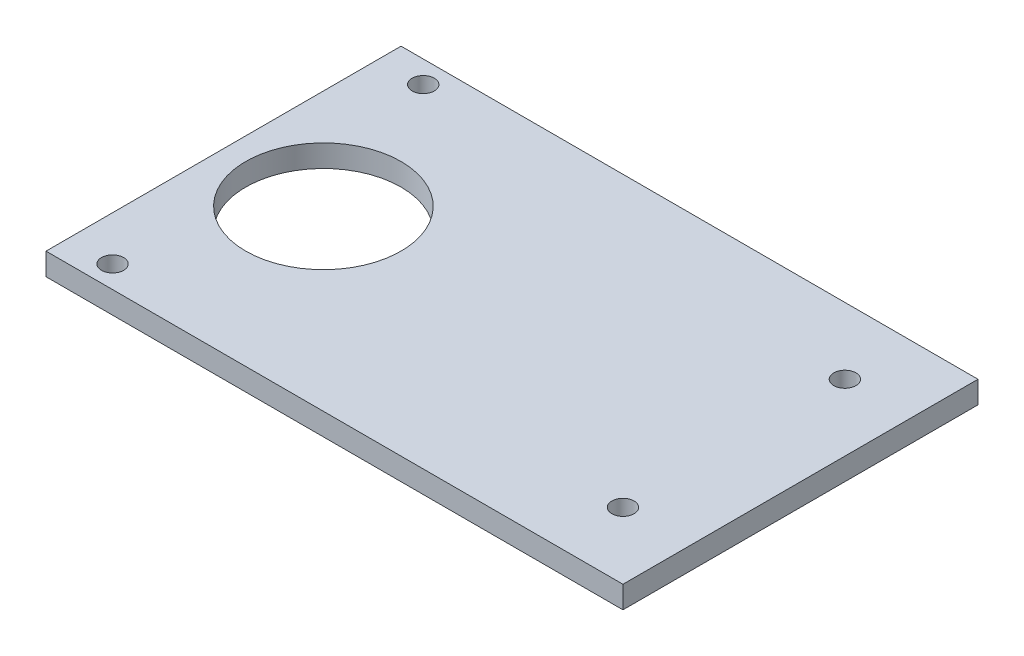
SolidWorks part; units mm, degrees
ref_plane "Front Plane" through (0, 0, 0) normal (0, 0, 1) x (1, 0, 0)
ref_plane "Top Plane" through (0, 0, 0) normal (0, 1, 0) x (1, 0, 0)
ref_plane "Right Plane" through (0, 0, 0) normal (1, 0, 0) x (0, 0, -1)
sketch "Sketch1" plane through (0, 0, 0) normal (0, 1, 0) x (1, 0, 0)
  line L0 (-69.7183, -5.3521) -> (60.2817, -5.3521) construction
  line L1 (-69.7183, 34.6479) -> (60.2817, 34.6479)
  line L2 (-69.7183, 34.6479) -> (-69.7183, -45.3521)
  line L3 (-69.7183, -45.3521) -> (60.2817, -45.3521)
  line L4 (60.2817, 34.6479) -> (60.2817, -45.3521)
  circle A0 centre (-47.2183, -5.3521) radius 17.5
  circle A1 centre (45.2817, 19.6479) radius 2.5
  circle A2 centre (-59.7183, 29.6479) radius 2.5
  circle A3 centre (45.2817, -30.3521) radius 2.5
  circle A4 centre (-59.7183, -40.3521) radius 2.5
  dimension "D3" = 35
  dimension "D4" = 5
  dimension "D5" = 5
  dimension "D6" = 15
  dimension "D7" = 15
  dimension "D8" = 5
  dimension "D9" = 10
  dimension "D10" = 22.5
  dimension "D1" = 130
  dimension "D2" = 80
extrude "Boss-Extrude1" add sketch "Sketch1" along normal blind 5
